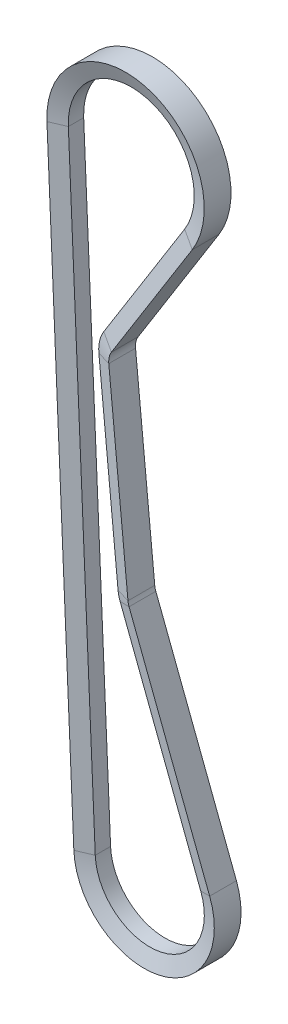
SolidWorks part; units mm, degrees
ref_plane "Front Plane" through (0, 0, 0) normal (0, 0, 1) x (1, 0, 0)
ref_plane "Top Plane" through (0, 0, 0) normal (0, 1, 0) x (1, 0, 0)
ref_plane "Right Plane" through (0, 0, 0) normal (1, 0, 0) x (0, 0, -1)
sketch "Sketch2" plane through (0, 0, 0) normal (0, 0, 1) x (1, 0, 0)
  line L0 (0, 0) -> (1, 0) construction
  line L1 (0, 0) -> (0, 1) construction
  line L12 (-24.9763, -1.0882) -> (-34.5514, 218.6829)
  line L14 (17.1555, 205.0448) -> (-11.6106, 159.0917)
  line L15 (-12.5478, 155.1026) -> (-5.7159, 85.4368)
  line L16 (-5.326, 83.7849) -> (23.3455, 8.9436)
  arc A4 (-34.5514, 218.6829) -> (17.1555, 205.0448) centre (-6.5779, 219.9016) cw
  arc A7 (23.3455, 8.9436) -> (-24.9763, -1.0882) centre (0, 0) cw
  arc A8 (-11.6106, 159.0917) -> (-12.5478, 155.1026) centre (-6.2282, 155.7224) ccw
  arc A9 (-5.7159, 85.4368) -> (-5.326, 83.7849) centre (0.6038, 86.0566) ccw
ref_plane "Plane4" through (23.3455, 8.9436, 0) normal (0.3577, -0.9338, 0) x (-0.9338, -0.3577, 0)
sketch "Sketch3" plane through (23.3455, 8.9436, 0) normal (0.3577, -0.9338, 0) x (-0.9338, -0.3577, 0)
  line L0 (0, -4.7625) -> (0, 4.7625)
  line L1 (0, -4.7625) -> (5.588, -2.7286)
  line L2 (5.588, -2.7286) -> (5.588, 2.7286)
  line L3 (5.588, 2.7286) -> (0, 4.7625)
  line L4 (0, 0) -> (5.588, 0) construction
  dimension "D1" = 9.525
  dimension "D2" = 5.588
  dimension "D3" = 40
sweep "Sweep1" add profiles "Sketch3" path "Sketch2"
